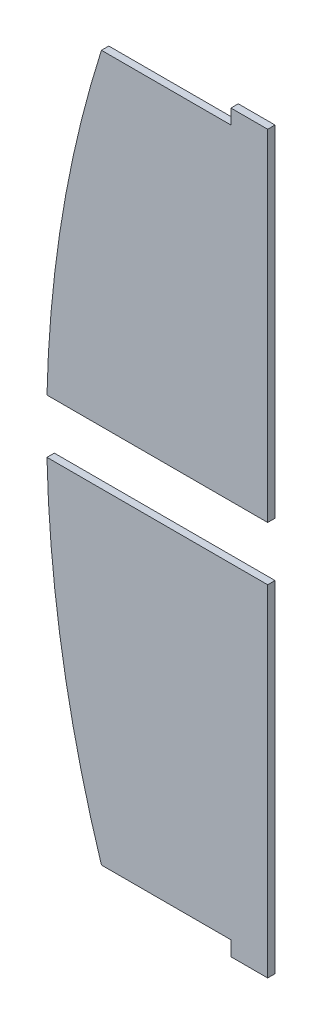
SolidWorks part; units mm, degrees
material "AISI 304"
ref_plane "Front Plane" through (0, 0, 0) normal (0, 0, 1) x (1, 0, 0)
ref_plane "Top Plane" through (0, 0, 0) normal (0, 1, 0) x (1, 0, 0)
ref_plane "Right Plane" through (0, 0, 0) normal (1, 0, 0) x (0, 0, -1)
sketch "Sketch1" plane through (0, 0, 0) normal (0, 0, 1) x (1, 0, 0)
  circle A0 centre (0, 0) radius 950
  circle A1 centre (0, 0) radius 840
  dimension "D1" = 1900
  dimension "D2" = 1680
base flange "Base-Flange1" sketch "Sketch1" thickness 6 reverse thickness direction no parameters "D1"=0
sketch "Sketch6" plane through (0, 0, 0) normal (0, 0, 1) x (1, 0, 0)
  line L1 (-1527.148, 300) -> (1205.8331, 300)
  line L2 (-1527.148, 300) -> (-1527.148, -300)
  line L3 (-1527.148, -300) -> (1205.8331, -300)
  line L4 (1205.8331, 300) -> (1205.8331, -300)
  line L5 (1951.6879, -1250.8317) -> (-1951.6879, -1250.8317)
  line L6 (1951.6879, -1250.8317) -> (1951.6879, 1250.8317)
  line L7 (1951.6879, 1250.8317) -> (-1951.6879, 1250.8317)
  line L8 (-1951.6879, -1250.8317) -> (-1951.6879, 1250.8317)
  line L9 (1951.6879, -1250.8317) -> (-1951.6879, 1250.8317) construction
  line L10 (1951.6879, 1250.8317) -> (-1951.6879, -1250.8317) construction
  point P4 (0, 0)
  dimension "283" = 300
  dimension "D2" = 300
extrude "Cut-Extrude1" cut sketch "Sketch6" against normal blind 10
sketch "Sketch7" plane through (0, 0, 0) normal (0, 0, 1) x (1, 0, 0)
  line L0 (-784.6018, 300) -> (-769.6018, 300)
  line L1 (-769.6018, 300) -> (-769.6018, -300)
  line L2 (-769.6018, -300) -> (-784.6018, -300)
  arc A0 (-784.6018, -300) -> (-784.6018, 300) centre (0, 0) cw
  dimension "D1" = 15
extrude "Boss-Extrude1" add sketch "Sketch7" against normal up to surface (6 mm away) up to face at (-868.9974, 0, -6)
sketch "Sketch8" plane through (0, 0, 0) normal (0, 0, 1) x (1, 0, 0)
  line L0 (-769.6018, -300) -> (-769.6018, 300) construction
  line L1 (-560.4589, -22) -> (-978.7448, -22)
  line L2 (-560.4589, -22) -> (-560.4589, 22)
  line L3 (-560.4589, 22) -> (-978.7448, 22)
  line L4 (-978.7448, -22) -> (-978.7448, 22)
  line L5 (-560.4589, -22) -> (-978.7448, 22) construction
  line L6 (-560.4589, 22) -> (-978.7448, -22) construction
  point P0 (-769.6018, 0)
  dimension "D1" = 44
extrude "Cut-Extrude2" cut sketch "Sketch8" against normal blind 10
sketch "Sketch13" plane through (0, 0, 0) normal (0, 0, 1) x (1, 0, 0)
  line L0 (-769.6018, 22) -> (-769.6018, 300) construction
  line L1 (-799.6018, 300) -> (-915.0075, 300)
  line L2 (-799.6018, 300) -> (-799.6018, 288)
  line L3 (-799.6018, 288) -> (-915.0075, 288)
  line L4 (-915.0075, 300) -> (-915.0075, 288)
  dimension "D1" = 12
  dimension "D2" = 30
extrude "Cut-Extrude3" cut sketch "Sketch13" against normal blind 10
sketch "Sketch14" plane through (0, 0, 0) normal (0, 0, 1) x (1, 0, 0)
  line L0 (-901.3878, -300) -> (-769.6018, -300) construction
  line L1 (-799.6018, -300) -> (-923.8401, -300)
  line L2 (-799.6018, -300) -> (-799.6018, -288)
  line L3 (-799.6018, -288) -> (-923.8401, -288)
  line L4 (-923.8401, -300) -> (-923.8401, -288)
  line L5 (-799.6018, 288) -> (-799.6018, 300) construction
  dimension "D1" = 12
extrude "Cut-Extrude4" cut sketch "Sketch14" against normal blind 10
sketch "Bend-Lines1" [suppressed] plane through (0, 0, 0) normal (0, 1, 0) x (1, 0, 0)
sketch "Bounding-Box1" [suppressed] plane through (0, 0, 0) normal (0, 1, 0) x (1, 0, 0)
sheet metal parameters "Sheet-Metal3" thickness 6 parameters "D1"=0
flat pattern "Flat-Pattern3" [suppressed]
sketch "Bend-Lines2" plane through (0, 0, 0) normal (0, 1, 0) x (1, 0, 0)
sketch3d "Bounding-Box2" [suppressed]
  line L0 (-461.3792, -1110.0129, 0) -> (1110.0131, -461.3787, 0) construction
  line L1 (-1110.0131, 461.3788, 0) -> (461.3792, 1110.0129, 0) construction
  line L2 (-461.3792, -1110.0129, 0) -> (-1110.0131, 461.3788, 0) construction
  line L3 (1110.0131, -461.3787, 0) -> (461.3792, 1110.0129, 0) construction
sheet metal parameters "Sheet-Metal5" thickness 6 parameters "D1"=0
flat pattern "Flat-Pattern3"
sketch "Bend-Lines2" plane through (0, 0, 0) normal (0, 1, 0) x (1, 0, 0)
sketch3d "Bounding-Box2" [suppressed]
  line L0 (-791.9596, 280, 0) -> (-791.9596, -280, 0) construction
  line L1 (-950, 280, 0) -> (-950, -280, 0) construction
  line L2 (-791.9596, 280, 0) -> (-950, 280, 0) construction
  line L3 (-791.9596, -280, 0) -> (-950, -280, 0) construction
sheet metal parameters "Sheet-Metal6" thickness 6 parameters "D1"=0
flat pattern "Flat-Pattern3"
sketch "Bend-Lines2" plane through (0, 0, 0) normal (0, 1, 0) x (1, 0, 0)
sketch3d "Bounding-Box2" [suppressed]
  line L0 (-769.6018, 300, 0) -> (-769.6018, -300, 0) construction
  line L1 (-950, 300, 0) -> (-950, -300, 0) construction
  line L2 (-769.6018, 300, 0) -> (-950, 300, 0) construction
  line L3 (-769.6018, -300, 0) -> (-950, -300, 0) construction
sheet metal parameters "Sheet-Metal7" thickness 6 parameters "D1"=0
flat pattern "Flat-Pattern7"
sketch "Bend-Lines3" plane through (0, 0, 0) normal (0, 1, 0) x (1, 0, 0)
sketch3d "Bounding-Box3" [suppressed]
  line L0 (-769.6018, 300, 0) -> (-769.6018, 22, 0) construction
  line L1 (-949.7452, 300, 0) -> (-949.7452, 22, 0) construction
  line L2 (-769.6018, 300, 0) -> (-949.7452, 300, 0) construction
  line L3 (-769.6018, 22, 0) -> (-949.7452, 22, 0) construction
sheet metal parameters "Sheet-Metal8" thickness 6 parameters "D1"=0
flat pattern "Flat-Pattern8"
sketch "Bend-Lines4" plane through (0, 0, 0) normal (0, 1, 0) x (1, 0, 0)
sketch3d "Bounding-Box4" [suppressed]
  line L0 (-769.6018, -22, 0) -> (-769.6018, -300, 0) construction
  line L1 (-949.7452, -22, 0) -> (-949.7452, -300, 0) construction
  line L2 (-769.6018, -22, 0) -> (-949.7452, -22, 0) construction
  line L3 (-769.6018, -300, 0) -> (-949.7452, -300, 0) construction
sheet metal parameters "Sheet-Metal9" thickness 6 parameters "D1"=0
flat pattern "Flat-Pattern7"
sketch "Bend-Lines3" plane through (0, 0, 0) normal (0, 1, 0) x (1, 0, 0)
sketch3d "Bounding-Box3" [suppressed]
  line L0 (-769.6018, 300, 0) -> (-769.6018, 22, 0) construction
  line L1 (-949.7452, 300, 0) -> (-949.7452, 22, 0) construction
  line L2 (-769.6018, 300, 0) -> (-949.7452, 300, 0) construction
  line L3 (-769.6018, 22, 0) -> (-949.7452, 22, 0) construction
sheet metal parameters "Sheet-Metal12" thickness 6 parameters "D1"=0
flat pattern "Flat-Pattern8"
sketch "Bend-Lines4" plane through (0, 0, 0) normal (0, 1, 0) x (1, 0, 0)
sketch3d "Bounding-Box4" [suppressed]
  line L0 (-769.6018, -22, 0) -> (-769.6018, -300, 0) construction
  line L1 (-949.7452, -22, 0) -> (-949.7452, -300, 0) construction
  line L2 (-769.6018, -22, 0) -> (-949.7452, -22, 0) construction
  line L3 (-769.6018, -300, 0) -> (-949.7452, -300, 0) construction
